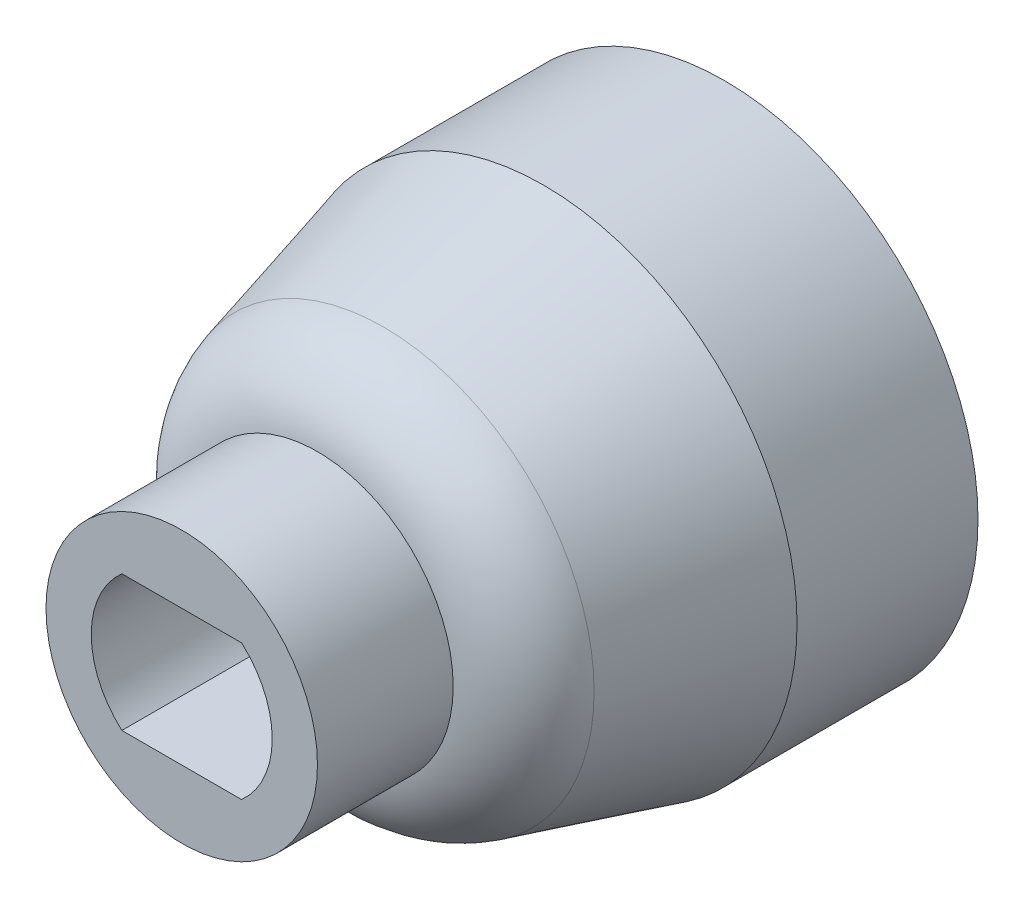
SolidWorks part; units mm, degrees
ref_plane "Front Plane" through (0, 0, 0) normal (0, 0, 1) x (1, 0, 0)
ref_plane "Top Plane" through (0, 0, 0) normal (0, 1, 0) x (1, 0, 0)
ref_plane "Right Plane" through (0, 0, 0) normal (1, 0, 0) x (0, 0, -1)
sketch "Sketch1" plane through (0, 0, 0) normal (0, 0, 1) x (1, 0, 0)
  circle A0 centre (0, 0) radius 5.6
  dimension "D1" = 11.2
extrude "Boss-Extrude1" add sketch "Sketch1" along normal blind 9
sketch "Sketch2" plane through (0, 0, 9) normal (0, 0, 1) x (1, 0, 0)
  line L0 (0, 1.5) -> (0, -1.5) construction
  line L1 (-1.3229, -1.5) -> (1.3229, -1.5)
  line L3 (-1.3229, 1.5) -> (1.3229, 1.5)
  circle A0 centre (0, 0) radius 3
  arc A1 (-1.3229, 1.5) -> (-1.3229, -1.5) centre (0, 0) ccw
  arc A2 (1.3229, -1.5) -> (1.3229, 1.5) centre (0, 0) ccw
  point P9 (0, -1.5)
  point P10 (0, 1.5)
  point P14 (0, 0)
  dimension "D1" = 6
  dimension "D2" = 4
  dimension "D3" = 3
extrude "Boss-Extrude2" add sketch "Sketch2" along normal blind 3
chamfer "Chamfer1" distance 5 angle 15 1 edges at (5.6, 0, 9) first distance on face at (5.6, 0, 9)
fillet "Fillet1" radius 2 1 edges at (4.2603, 0, 9)
